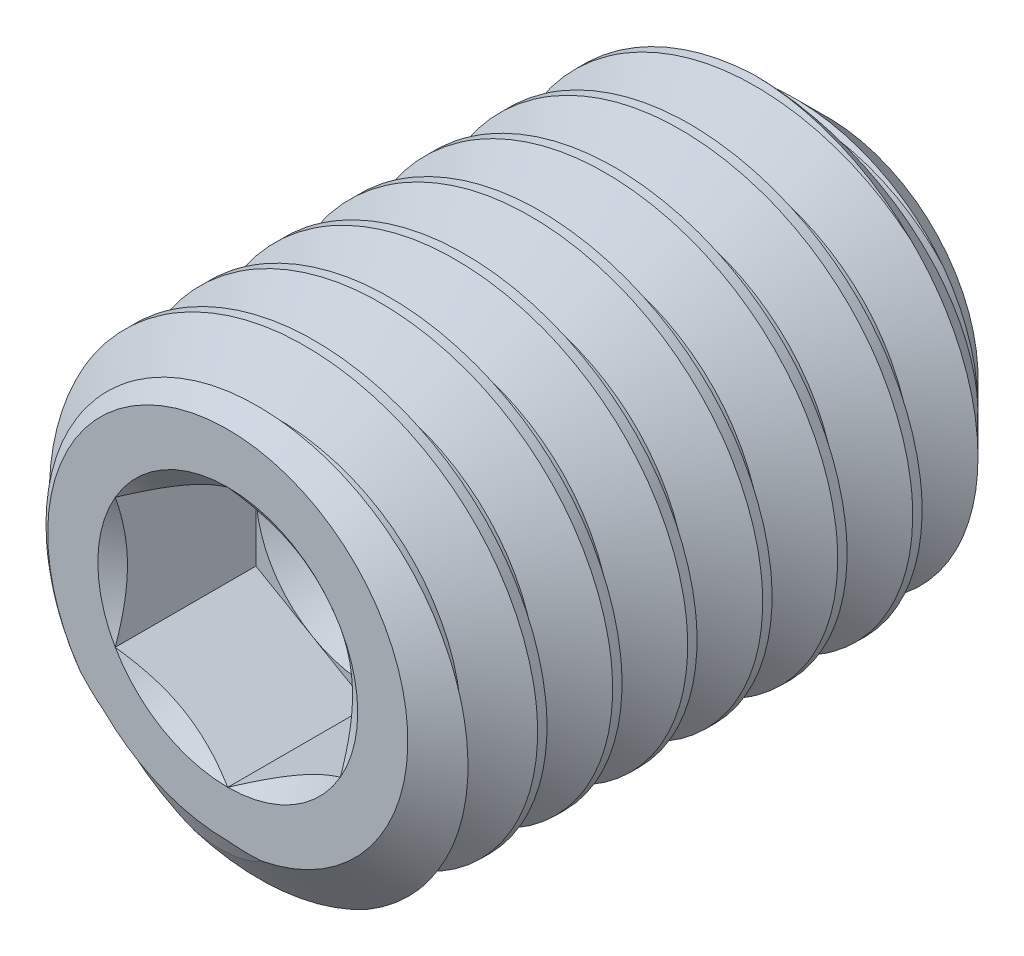
SolidWorks part; units mm, degrees
ref_plane "Front" through (0, 0, 0) normal (0, 0, 1) x (1, 0, 0)
ref_plane "Top" through (0, 0, 0) normal (0, 1, 0) x (1, 0, 0)
ref_plane "Right" through (0, 0, 0) normal (1, 0, 0) x (0, 0, -1)
sketch "Sketch22" plane through (0, 0, 0) normal (1, 0, 0) x (0, 0, -1)
  line L0 (-2, 0) -> (-2, 1.2)
  line L1 (-2, 1.2) -> (-1.7899, 1.5)
  line L2 (-1.7899, 1.5) -> (1.5, 1.5)
  line L3 (1.5, 1.5) -> (2, 1)
  line L4 (-0.145, 1.5) -> (-0.145, -1.5) construction
  line L5 (2, 0) -> (-2, 0)
  line L6 (-2, 1.2) -> (-2, -1.2) construction
  line L7 (2, 0) -> (2, 1)
  point P11 (-0.145, 0)
  dimension "D1" = 2.4
  dimension "Dia" = 3
  dimension "D2" = 0.5
  dimension "Length" = 4
  dimension "D3" = 35
  dimension "D6" = 45
revolve "Revolve1" add sketch "Sketch22" angle 360 about L5
ref_plane "Plane1" through (0, 0, -2) normal (0, 0, 1) x (1, 0, 0)
sketch "Sketch27" plane through (0, 0, -2) normal (0, 0, 1) x (1, 0, 0)
  circle A0 centre (0, 0) radius 1.5 construction
  circle A1 centre (0, 0) radius 1.5
curve "Helix/Spiral1" pitch 0.5 height 4.5 radius 1.5 centre (0, 0, -2) axis (0, 0, 1) start towards (0, 1, 0)
sketch "Sketch28" plane through (0, 0, 0) normal (1, 0, 0) x (0, 0, -1)
  line L0 (2, 1.5) -> (2.4375, 1.5)
  line L1 (2.4375, 1.5) -> (2.25, 1.1752)
  line L2 (2.25, 1.1752) -> (2.1875, 1.1752)
  line L3 (2.1875, 1.1752) -> (2, 1.5)
  line L4 (2.0938, 1.3376) -> (2.3438, 1.3376) construction
  line L6 (-1.7899, 1.5) -> (1.5, 1.5) construction
  dimension "D1" = 0.0625
  dimension "D2" = 0.25
  dimension "D3" = 60
sweep "Cut-Sweep2" cut profiles "Sketch28" path "Helix/Spiral1"
sketch "Sketch23" plane through (0, 0, 2) normal (0, 0, 1) x (1, 0, 0)
  line L1 (0, 0.866) -> (-0.75, 0.433)
  line L2 (-0.75, 0.433) -> (-0.75, -0.433)
  line L3 (-0.75, -0.433) -> (0, -0.866)
  line L4 (0, -0.866) -> (0.75, -0.433)
  line L5 (0.75, -0.433) -> (0.75, 0.433)
  line L6 (0.75, 0.433) -> (0, 0.866)
  circle A0 centre (0, 0) radius 0.75 construction
  dimension "Hex" = 1.5
extrude "Cut-Extrude10" cut sketch "Sketch23" against normal blind 0.9375
sketch "Sketch24" plane through (0, 0, 2) normal (0, 0, 1) x (1, 0, 0)
  circle A0 centre (0, 0) radius 0.866
extrude "Cut-Extrude11" cut sketch "Sketch24" against normal through all draft 55
sketch "Sketch26" plane through (0, 0, 1.0625) normal (0, 0, 1) x (1, 0, 0)
  circle A0 centre (0, 0) radius 0.75 construction
  circle A1 centre (0, 0) radius 0.75
extrude "Cut-Extrude12" cut sketch "Sketch26" against normal through all draft 60
sketch "Sketch30" plane through (0, 0, 0) normal (1, 0, 0) x (0, 0, -1)
  line L0 (-1.7899, 1.5) -> (1.5, 1.5) construction
  line L1 (-2, 0) -> (-2, 1.2) construction
  line L2 (2, 0) -> (2, 1) construction
  point P0 (-2, 1.5)
  point P1 (2, 1.5)
  point P2 (2, -1.5)
  point P11 (0.75, -1.5)
  dimension "D1" = 1.25
equation "\"D1@Sketch28\" = \"D4@Helix/Spiral1\" * .125"
equation "\"D2@Sketch28\" = \"D4@Helix/Spiral1\" * .5"
equation "\"D3@Helix/Spiral1\" = \"Length@Sketch22\" + \"D4@Helix/Spiral1\""
equation "\"D1@Sketch30\" = \"D4@Helix/Spiral1\" * 2.5"
equation "\"hex Depth@Cut-Extrude10\" = \"Hex@Sketch23\" * .625"
equation "\"D1@Sketch22\" = \"Dia@Sketch22\" * .8"
equation "\"D2@Sketch22\" = \"D4@Helix/Spiral1\""
